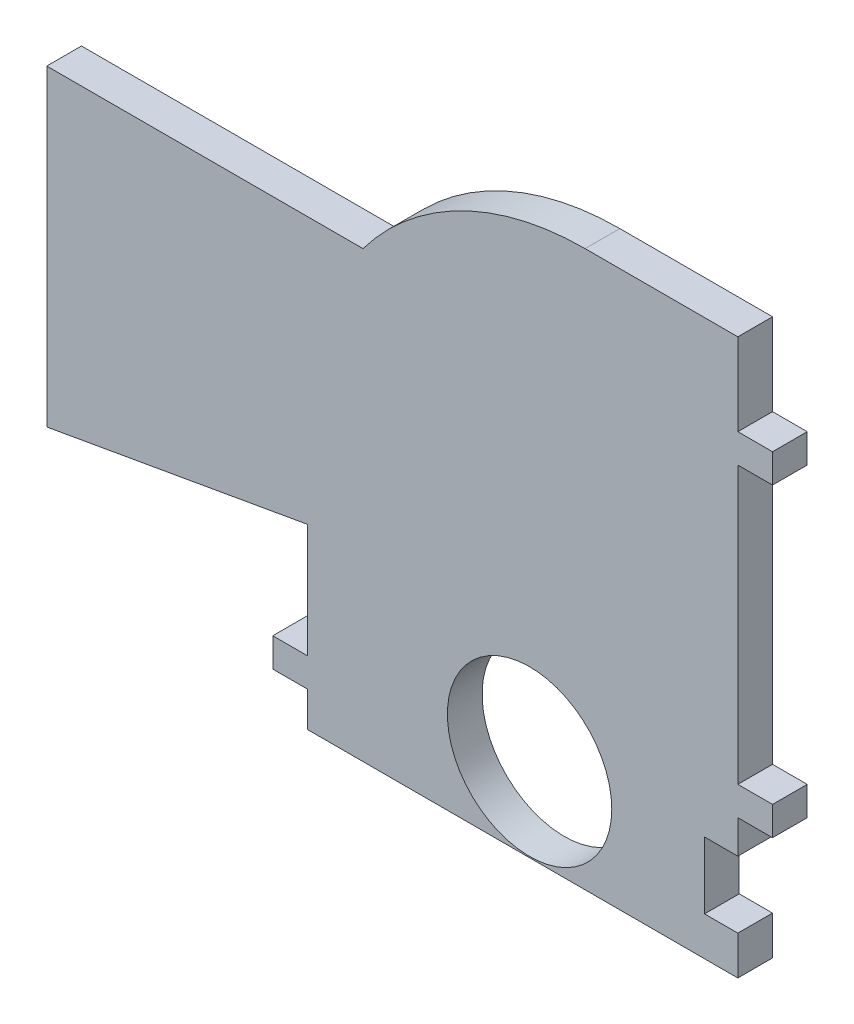
SolidWorks part; units mm, degrees
material "Balsa"
ref_plane "Front Plane" through (0, 0, 0) normal (0, 0, 1) x (1, 0, 0)
ref_plane "Top Plane" through (0, 0, 0) normal (0, 1, 0) x (1, 0, 0)
ref_plane "Right Plane" through (0, 0, 0) normal (1, 0, 0) x (0, 0, -1)
sketch "Sketch1" plane through (0, 0, 0) normal (0, 0, 1) x (1, 0, 0)
  line L0 (0, -1000.1535) -> (0, 48999.8465) construction
  line L1 (-7.62, 16.51) -> (-22.0849, 16.51)
  line L2 (-1000, 0) -> (49000, 0) construction
  line L3 (9.525, 16.51) -> (11.1125, 16.51)
  line L4 (2.54, 21.59) -> (9.525, 21.59)
  line L5 (-10.16, 8.89) -> (-10.16, -3.81)
  line L6 (-10.16, -3.81) -> (9.525, -3.81)
  line L7 (9.525, 21.59) -> (9.525, -3.81)
  line L8 (-11.7475, -2.2098) -> (-10.16, -2.2098)
  line L9 (-11.7475, -2.2098) -> (-11.7475, -0.889)
  line L10 (-11.7475, -0.889) -> (-10.16, -0.889)
  line L11 (-10.16, -2.2098) -> (-10.16, -0.889)
  line L12 (9.525, 2.54) -> (11.1125, 2.54)
  line L13 (9.525, 2.54) -> (9.525, 3.8608)
  line L14 (9.525, 3.8608) -> (11.1125, 3.8608)
  line L15 (11.1125, 2.54) -> (11.1125, 3.8608)
  line L16 (9.525, 16.51) -> (9.525, 17.8308)
  line L17 (9.525, 17.8308) -> (11.1125, 17.8308)
  line L18 (11.1125, 16.51) -> (11.1125, 17.8308)
  line L20 (-22.0849, 2.212) -> (-10.16, 4.318)
  line L22 (-22.0849, 13.081) -> (-22.0849, 4.699)
  line L26 (-22.0849, 13.081) -> (-22.0849, 16.51)
  line L27 (9.525, 1.016) -> (8.001, 1.016)
  line L28 (9.525, 1.016) -> (9.525, -2.032)
  line L29 (9.525, -2.032) -> (8.001, -2.032)
  line L30 (8.001, 1.016) -> (8.001, -2.032)
  line L31 (-22.0849, 4.699) -> (-22.0849, 2.212)
  circle A0 centre (0, 0) radius 3.7592
  arc A3 (2.54, 21.59) -> (-10.16, 8.89) centre (2.54, 8.89) ccw
  dimension "D1" = 7.5184
  dimension "D4" = 3.81
  dimension "D3" = 3.7592
  dimension "D5" = 1.5875
  dimension "D9" = 12.7
  dimension "D10" = 1.5875
  dimension "D18" = 11.9249
  dimension "D2" = 25.4
  dimension "D6" = 9.525
  dimension "D7" = 1.3208
  dimension "D8" = 19.685
  dimension "D11" = 2.54
  dimension "D12" = 1.3208
  dimension "D13" = 1.3208
  dimension "D14" = 1.5875
  dimension "D15" = 1.524
  dimension "D16" = 1.016
  dimension "D17" = 3.048
  dimension "D19" = 5.08
  dimension "D20" = 8.128
  dimension "D21" = 14.298
  dimension "D22" = 5.207
extrude "Boss-Extrude1" add sketch "Sketch1" along normal blind 1.5875 contours L4 A3 L5 L6 L7 A0 | L10 L9 L8 L5 | L3 L18 L17 L7 | L12 L15 L14 L7 | A3 L1 L20 L5 | L20 region at (-16.0223, 10.0529, 0) region at (0.1298, 9.1228, 0) region at (10.3187, 17.1704, 0) region at (-10.9538, -1.5494, 0) region at (10.3187, 3.2004, 0)
move or copy body "Body-Move/Copy1" [suppressed] bodies to move or copy 101
